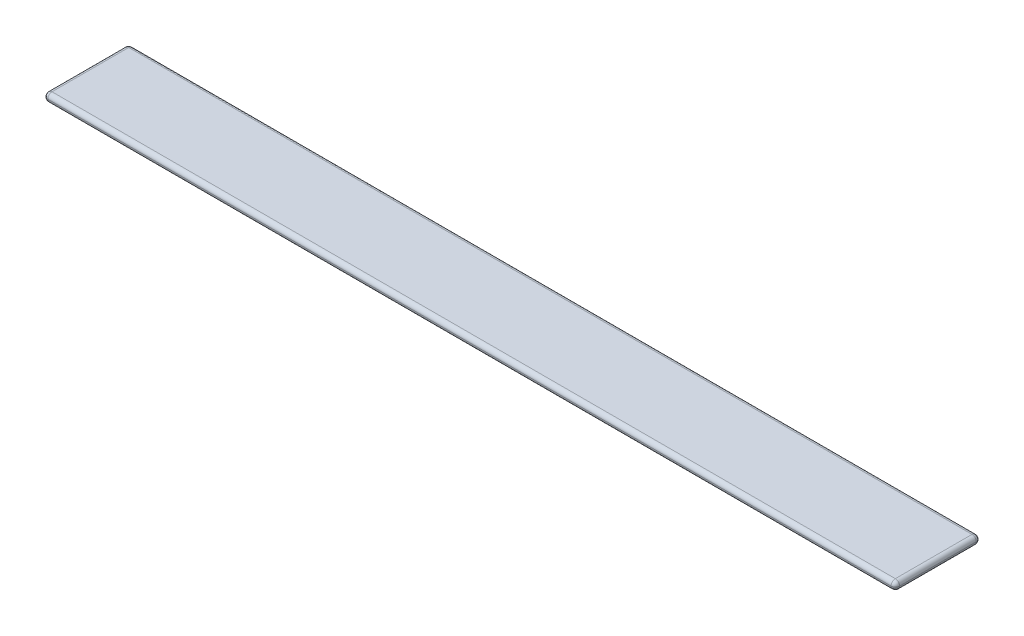
SolidWorks part; units mm, degrees
ref_plane "Front Plane" through (0, 0, 0) normal (0, 0, 1) x (1, 0, 0)
ref_plane "Top Plane" through (0, 0, 0) normal (0, 1, 0) x (1, 0, 0)
ref_plane "Right Plane" through (0, 0, 0) normal (1, 0, 0) x (0, 0, -1)
sketch "Sketch1" plane through (0, 0, 0) normal (0, 1, 0) x (1, 0, 0)
  line L1 (0, 0) -> (50, 0)
  line L2 (0, 0) -> (0, -5)
  line L3 (0, -5) -> (50, -5)
  line L4 (50, 0) -> (50, -5)
  dimension "D1" = 50
  dimension "D2" = 5
extrude "Boss-Extrude1" add sketch "Sketch1" along normal blind 0.5
fillet "Fillet3" radius 0.25 8 edges at (0, 0, 2.5) (0, 0.5, 2.5) (25, 0.5, 0) (25, 0, 0) (25, 0, 5) (25, 0.5, 5) (50, 0.5, 2.5) (50, 0, 2.5)
